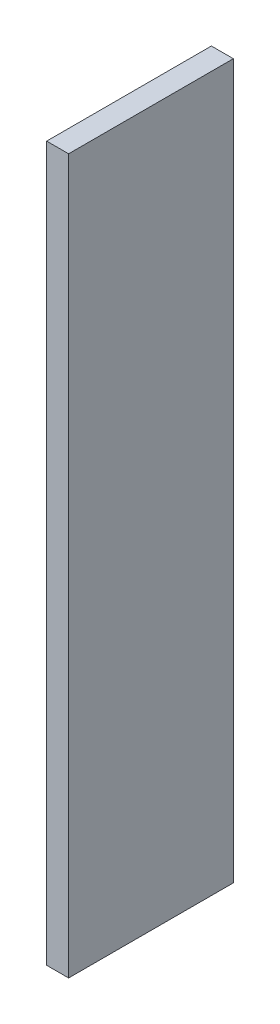
SolidWorks part; units mm, degrees
ref_plane "Front Plane" through (0, 0, 0) normal (0, 0, 1) x (1, 0, 0)
ref_plane "Top Plane" through (0, 0, 0) normal (0, 1, 0) x (1, 0, 0)
ref_plane "Right Plane" through (0, 0, 0) normal (1, 0, 0) x (0, 0, -1)
sketch "Sketch1" plane through (0, 0, 0) normal (0, 0, 1) x (1, 0, 0)
  line L1 (0, 0) -> (0.4, 0)
  line L2 (0, 0) -> (0, 13)
  line L3 (0, 13) -> (0.4, 13)
  line L4 (0.4, 0) -> (0.4, 13)
  dimension "D2" = 13
extrude "Boss-Extrude1" add sketch "Sketch1" along normal blind 3
equation "\"A.L\"= 0.07m"
equation "\"A.h\"= 0.007m"
equation "\"A.d\"= 0.003m"
equation "\"A.delta\"= 45.0001"
equation "\"A.w\"= 0.02m"
equation "\"A.v\"= 0.03m"
equation "\"A.s\"= 0.014m"
equation "\"A.t\"= 0.007m"
equation "\"B.L\"= 0.065m"
equation "\"B.h\"= 0.008m"
equation "\"B.s\"= 0.016m"
equation "\"B.t\"= 0.008m"
equation "\"C.h\"= 0.0065m"
equation "\"C.d\"= 0.003m"
equation "\"C.L\"= 0.05m"
equation "\"C.wmax\"= 0.005m"
equation "\"D.L\"= 0.06m"
equation "\"D.h\"= 0.008m"
equation "\"D.s\"= 0.012m"
equation "\"D.t\"= 0.008m"
equation "\"a_h\"= 0.0002m"
equation "\"a_d\"= 0.003m"
equation "\"a_L\"= 0.008m"
equation "\"b_h\"= 0.0004m"
equation "\"b_d\"= 0.003m"
equation "\"b_L\"= 0.007m"
equation "\"c_h\"= 0.0001m"
equation "\"c_d\"= 0.003m"
equation "\"c_L\"= 0.01m"
equation "\"d_h\"= 0.0001m"
equation "\"d_d\"= 0.003m"
equation "\"d_L\"= 0.01m"
equation "\"S.h\"= 0.015m"
equation "\"S.L\"= 0.09075m"
equation "\"D1@Sketch1\"=\"b_h\""
equation "\"D2@Sketch1\"=\"b_L\"+0.006"
equation "\"D1@Boss-Extrude1\"=\"b_d\""
